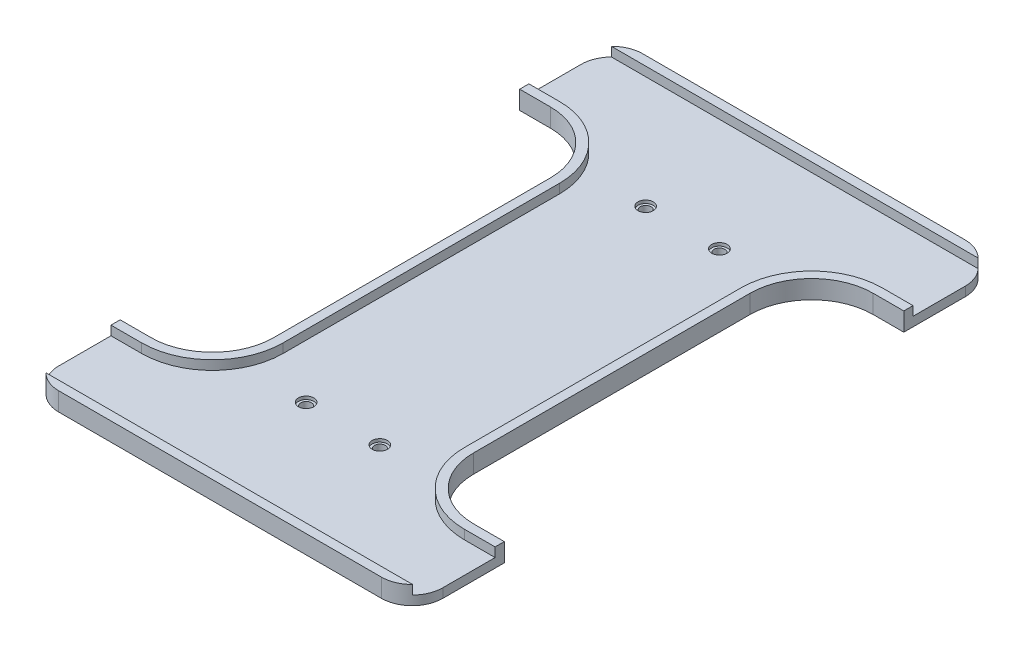
SolidWorks part; units mm, degrees
ref_plane "Front Plane" through (0, 0, 0) normal (0, 0, 1) x (1, 0, 0)
ref_plane "Top Plane" through (0, 0, 0) normal (0, 1, 0) x (1, 0, 0)
ref_plane "Right Plane" through (0, 0, 0) normal (1, 0, 0) x (0, 0, -1)
sketch "Sketch1" plane through (0, 0, 0) normal (0, 1, 0) x (1, 0, 0)
  line L0 (0, 95) -> (0, -95) construction
  line L1 (-62.5, -95) -> (62.5, -95)
  line L2 (-62.5, -95) -> (-62.5, 95)
  line L3 (-62.5, 95) -> (62.5, 95)
  line L4 (62.5, -95) -> (62.5, 95)
  line L5 (-62.5, -95) -> (62.5, 95) construction
  line L6 (-62.5, 95) -> (62.5, -95) construction
  circle A0 centre (-12, -55) radius 1.75
  circle A1 centre (12, -55) radius 1.75
  circle A2 centre (-12, 55.5) radius 1.75
  circle A3 centre (12, 55.5) radius 1.75
  circle A4 centre (12, -55) radius 2.5
  circle A5 centre (-12, -55) radius 2.5
  circle A6 centre (12, 55.5) radius 2.5
  circle A7 centre (-12, 55.5) radius 2.5
  point P0 (0, 0)
  dimension "D3" = 3.5
  dimension "D8" = 5
  dimension "D1" = 125
  dimension "D2" = 190
  dimension "D4" = 24
  dimension "D5" = 24
  dimension "D6" = 40
  dimension "D7" = 110.5
extrude "Boss-Extrude1" add sketch "Sketch1" along normal blind 3 contours L1 L4 L3 L2 A7 A6 A5 A4 | A5 A0 | A4 A1 | A6 A3 | A7 A2 region at (0, 0, 0.0008) region at (9.5707, 0, 55) region at (-14.4293, 0, 55) region at (9.5707, 0, -55.5) region at (-14.4293, 0, -55.5)
extrude "Cut-Extrude1" cut sketch "Sketch1<3>" against normal blind 1 from surface contours A5 A0 | A6 A3 | A7 A2 | A4 A1 region at (9.5707, 0, 55) region at (-14.4293, 0, 55) region at (9.5707, 0, -55.5) region at (-14.4293, 0, -55.5) starting at face at (0, 3, 0)
sketch "Sketch1<3>" plane through (0, 0, 0) normal (0, 1, 0) x (1, 0, 0) same geometry as "Sketch1"
sketch "Sketch2" plane through (0, 3, 0) normal (0, 1, 0) x (1, 0, 0)
  line L0 (62.5, -65) -> (32.5, -65)
  line L1 (62.5, -95) -> (62.5, 95) construction
  line L2 (32.5, -65) -> (32.5, 65)
  line L3 (32.5, 65) -> (62.5, 65)
  line L4 (-62.5, -95) -> (62.5, -95) construction
  line L5 (-62.5, 95) -> (62.5, 95) construction
  line L6 (0, 95) -> (0, -95) construction
  line L7 (-32.5, 65) -> (-62.5, 65)
  line L8 (-32.5, -65) -> (-32.5, 65)
  line L9 (-62.5, -65) -> (-32.5, -65)
  line L10 (62.5, 65) -> (62.5, -65)
  line L11 (-62.5, 65) -> (-62.5, -65)
  dimension "D1" = 30
  dimension "D2" = 30
  dimension "D3" = 30
extrude "Cut-Extrude2" cut sketch "Sketch2" against normal through all
fillet "Fillet1" radius 20 4 edges at (32.5, 1.5, -65) (-32.5, 1.5, -65) (-32.5, 1.5, 65) (32.5, 1.5, 65)
fillet "Fillet2" radius 10 4 edges at (62.5, 1.5, -95) (-62.5, 1.5, -95) (-62.5, 1.5, 95) (62.5, 1.5, 95)
sketch "Sketch3" plane through (0, 3, 0) normal (0, 1, 0) x (1, 0, 0)
  line L1 (-59.5, 68) -> (-62.5, 68)
  line L2 (-62.5, 85) -> (-62.5, 65) construction
  line L4 (59.5, 68) -> (62.5, 68)
  line L5 (62.5, 65) -> (62.5, 85) construction
  line L6 (-52.5, -92) -> (-59.6414, -92)
  line L7 (52.5, -92) -> (59.6414, -92)
  line L8 (-52.5, 92) -> (-59.6414, 92)
  line L9 (52.5, 92) -> (59.6414, 92)
  line L13 (52.5, 92) -> (-52.5, 92)
  line L15 (-59.5, 68) -> (-52.5, 68)
  line L16 (-29.5, 45) -> (-29.5, -45)
  line L17 (-52.5, -68) -> (-59.5, -68)
  line L19 (-52.5, -92) -> (52.5, -92)
  line L21 (59.5, -68) -> (52.5, -68)
  line L22 (29.5, -45) -> (29.5, 45)
  line L23 (52.5, 68) -> (59.5, 68)
  line L24 (62.5, 65) -> (62.5, 85)
  line L25 (52.5, 95) -> (-52.5, 95)
  line L26 (-62.5, 85) -> (-62.5, 65)
  line L27 (-62.5, 65) -> (-52.5, 65)
  line L28 (-32.5, 45) -> (-32.5, -45)
  line L29 (-52.5, -65) -> (-62.5, -65)
  line L30 (-62.5, -65) -> (-62.5, -85)
  line L31 (-52.5, -95) -> (52.5, -95)
  line L32 (62.5, -85) -> (62.5, -65)
  line L33 (62.5, -65) -> (52.5, -65)
  line L34 (32.5, -45) -> (32.5, 45)
  line L35 (52.5, 65) -> (62.5, 65)
  line L36 (62.5, 65) -> (62.5, 68)
  line L37 (52.5, 95) -> (-52.5, 95)
  line L38 (-62.5, 68) -> (-62.5, 65)
  line L39 (-62.5, 65) -> (-52.5, 65)
  line L40 (-32.5, 45) -> (-32.5, -45)
  line L41 (-52.5, -65) -> (-62.5, -65)
  line L42 (-62.5, -65) -> (-62.5, -68)
  line L43 (-52.5, -95) -> (52.5, -95)
  line L44 (62.5, -68) -> (62.5, -65)
  line L45 (62.5, -65) -> (52.5, -65)
  line L46 (32.5, -45) -> (32.5, 45)
  line L47 (52.5, 65) -> (62.5, 65)
  line L48 (-59.5, -68) -> (-62.5, -68)
  line L50 (-62.5, -65) -> (-62.5, -85) construction
  line L52 (59.5, -68) -> (62.5, -68)
  line L53 (62.5, -85) -> (62.5, -65) construction
  line L60 (-59.5, -68) -> (-59.5, -85) construction
  line L61 (59.5, -85) -> (59.5, -68) construction
  line L62 (-59.5, 85) -> (-59.5, 68) construction
  line L63 (59.5, 68) -> (59.5, 85) construction
  arc A0 (52.5, -92) -> (59.5, -85) centre (52.5, -85) ccw construction
  arc A1 (52.5, -95) -> (62.5, -85) centre (52.5, -85) ccw construction
  arc A2 (-52.5, 92) -> (-59.5, 85) centre (-52.5, 85) ccw construction
  arc A3 (-52.5, 95) -> (-62.5, 85) centre (-52.5, 85) ccw construction
  arc A4 (62.5, 85) -> (52.5, 95) centre (52.5, 85) ccw construction
  arc A5 (59.5, 85) -> (52.5, 92) centre (52.5, 85) ccw construction
  arc A10 (-29.5, 45) -> (-52.5, 68) centre (-52.5, 45) ccw
  arc A11 (-52.5, -68) -> (-29.5, -45) centre (-52.5, -45) ccw
  arc A14 (29.5, -45) -> (52.5, -68) centre (52.5, -45) ccw
  arc A15 (52.5, 68) -> (29.5, 45) centre (52.5, 45) ccw
  arc A16 (62.5, 85) -> (52.5, 95) centre (52.5, 85) ccw
  arc A17 (-52.5, 95) -> (-62.5, 85) centre (-52.5, 85) ccw
  arc A18 (-32.5, 45) -> (-52.5, 65) centre (-52.5, 45) ccw
  arc A19 (-52.5, -65) -> (-32.5, -45) centre (-52.5, -45) ccw
  arc A20 (-62.5, -85) -> (-52.5, -95) centre (-52.5, -85) ccw
  arc A21 (52.5, -95) -> (62.5, -85) centre (52.5, -85) ccw
  arc A22 (32.5, -45) -> (52.5, -65) centre (52.5, -45) ccw
  arc A23 (52.5, 65) -> (32.5, 45) centre (52.5, 45) ccw
  arc A24 (59.6414, 92) -> (52.5, 95) centre (52.5, 85) ccw
  arc A25 (-52.5, 95) -> (-59.6414, 92) centre (-52.5, 85) ccw
  arc A26 (-32.5, 45) -> (-52.5, 65) centre (-52.5, 45) ccw
  arc A27 (-52.5, -65) -> (-32.5, -45) centre (-52.5, -45) ccw
  arc A28 (-59.6414, -92) -> (-52.5, -95) centre (-52.5, -85) ccw
  arc A29 (52.5, -95) -> (59.6414, -92) centre (52.5, -85) ccw
  arc A30 (32.5, -45) -> (52.5, -65) centre (52.5, -45) ccw
  arc A31 (52.5, 65) -> (32.5, 45) centre (52.5, 45) ccw
  arc A32 (-59.5, -85) -> (-52.5, -92) centre (-52.5, -85) ccw construction
  arc A33 (-62.5, -85) -> (-52.5, -95) centre (-52.5, -85) ccw construction
  dimension "D1" = 0
  dimension "D2" = 3
extrude "Boss-Extrude2" add sketch "Sketch3" along normal blind 3
sketch "Sketch4" plane through (0, 3, 0) normal (0, 1, 0) x (1, 0, 0)
  line L0 (3.4641, 16) -> (1.7321, 19)
  line L1 (3.4641, 0) -> (1.7321, 3)
  line L2 (1.7321, 3) -> (-1.7321, 3)
  line L3 (-1.7321, 3) -> (-3.4641, 0)
  line L4 (-3.4641, 0) -> (-1.7321, -3)
  line L5 (-1.7321, -3) -> (1.7321, -3)
  line L6 (1.7321, -3) -> (3.4641, 0)
  line L7 (1.7321, 19) -> (-1.7321, 19)
  line L8 (-1.7321, 19) -> (-3.4641, 16)
  line L9 (-3.4641, 16) -> (-1.7321, 13)
  line L10 (-1.7321, 13) -> (1.7321, 13)
  line L11 (1.7321, 13) -> (3.4641, 16)
  line L12 (3.4641, 32) -> (1.7321, 35)
  line L13 (1.7321, 35) -> (-1.7321, 35)
  line L14 (-1.7321, 35) -> (-3.4641, 32)
  line L15 (-3.4641, 32) -> (-1.7321, 29)
  line L16 (-1.7321, 29) -> (1.7321, 29)
  line L17 (1.7321, 29) -> (3.4641, 32)
  line L18 (3.4641, 48) -> (1.7321, 51)
  line L19 (1.7321, 51) -> (-1.7321, 51)
  line L20 (-1.7321, 51) -> (-3.4641, 48)
  line L21 (-3.4641, 48) -> (-1.7321, 45)
  line L22 (-1.7321, 45) -> (1.7321, 45)
  line L23 (1.7321, 45) -> (3.4641, 48)
  line L24 (3.4641, 64) -> (1.7321, 67)
  line L25 (1.7321, 67) -> (-1.7321, 67)
  line L26 (-1.7321, 67) -> (-3.4641, 64)
  line L27 (-3.4641, 64) -> (-1.7321, 61)
  line L28 (-1.7321, 61) -> (1.7321, 61)
  line L29 (1.7321, 61) -> (3.4641, 64)
  line L30 (3.4641, 80) -> (1.7321, 83)
  line L31 (1.7321, 83) -> (-1.7321, 83)
  line L32 (-1.7321, 83) -> (-3.4641, 80)
  line L33 (-3.4641, 80) -> (-1.7321, 77)
  line L34 (-1.7321, 77) -> (1.7321, 77)
  line L35 (1.7321, 77) -> (3.4641, 80)
  line L36 (-29.5, 0) -> (29.5, 0) construction
  line L37 (-29.5, -45) -> (-29.5, 45) construction
  line L38 (29.5, 45) -> (29.5, -45) construction
  line L39 (1.7321, -77) -> (3.4641, -80)
  line L40 (-1.7321, -77) -> (1.7321, -77)
  line L41 (-3.4641, -80) -> (-1.7321, -77)
  line L42 (-1.7321, -83) -> (-3.4641, -80)
  line L43 (1.7321, -83) -> (-1.7321, -83)
  line L44 (3.4641, -80) -> (1.7321, -83)
  line L45 (1.7321, -61) -> (3.4641, -64)
  line L46 (-1.7321, -61) -> (1.7321, -61)
  line L47 (-3.4641, -64) -> (-1.7321, -61)
  line L48 (-1.7321, -67) -> (-3.4641, -64)
  line L49 (1.7321, -67) -> (-1.7321, -67)
  line L50 (3.4641, -64) -> (1.7321, -67)
  line L51 (1.7321, -45) -> (3.4641, -48)
  line L52 (-1.7321, -45) -> (1.7321, -45)
  line L53 (-3.4641, -48) -> (-1.7321, -45)
  line L54 (-1.7321, -51) -> (-3.4641, -48)
  line L55 (1.7321, -51) -> (-1.7321, -51)
  line L56 (3.4641, -48) -> (1.7321, -51)
  line L57 (1.7321, -29) -> (3.4641, -32)
  line L58 (-1.7321, -29) -> (1.7321, -29)
  line L59 (-3.4641, -32) -> (-1.7321, -29)
  line L60 (-1.7321, -35) -> (-3.4641, -32)
  line L61 (1.7321, -35) -> (-1.7321, -35)
  line L62 (3.4641, -32) -> (1.7321, -35)
  line L63 (1.7321, -13) -> (3.4641, -16)
  line L64 (-1.7321, -13) -> (1.7321, -13)
  line L65 (-3.4641, -16) -> (-1.7321, -13)
  line L66 (-1.7321, -19) -> (-3.4641, -16)
  line L67 (1.7321, -19) -> (-1.7321, -19)
  line L68 (3.4641, -16) -> (1.7321, -19)
  circle A0 centre (0, 0) radius 3 construction
  dimension "D1" = 6
  dimension "D2" = 6
